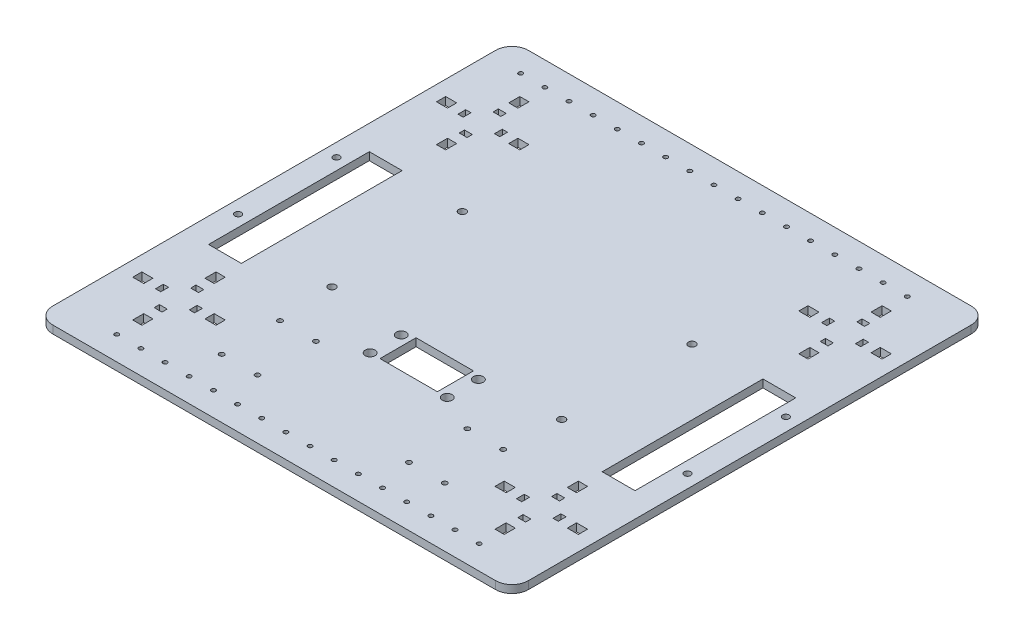
SolidWorks part; units mm, degrees
ref_plane "Front Plane" through (0, 0, 0) normal (0, 0, 1) x (1, 0, 0)
ref_plane "Top Plane" through (0, 0, 0) normal (0, 1, 0) x (1, 0, 0)
ref_plane "Right Plane" through (0, 0, 0) normal (1, 0, 0) x (0, 0, -1)
sketch "Sketch1" plane through (0, 0, 0) normal (0, 1, 0) x (1, 0, 0)
  line L0 (-145, 130.5) -> (145, 130.5) construction
  line L1 (145, -145) -> (-145, -145)
  line L2 (145, -145) -> (145, 145)
  line L3 (145, 145) -> (-145, 145)
  line L4 (-145, -145) -> (-145, 145)
  line L5 (145, -145) -> (-145, 145) construction
  line L6 (145, 145) -> (-145, -145) construction
  line L7 (-145, 116) -> (145, 116) construction
  line L8 (-145, 101.5) -> (145, 101.5) construction
  line L9 (-145, 87) -> (145, 87) construction
  line L10 (-145, 72.5) -> (145, 72.5) construction
  line L11 (-145, 58) -> (145, 58) construction
  line L12 (-145, 43.5) -> (145, 43.5) construction
  line L13 (-145, 29) -> (145, 29) construction
  line L14 (-145, 14.5) -> (145, 14.5) construction
  line L15 (-145, 0) -> (145, 0) construction
  line L16 (-145, -14.5) -> (145, -14.5) construction
  line L17 (-145, -29) -> (145, -29) construction
  line L18 (-145, -43.5) -> (145, -43.5) construction
  line L19 (-145, -58) -> (145, -58) construction
  line L20 (-145, -72.5) -> (145, -72.5) construction
  line L21 (-145, -87) -> (145, -87) construction
  line L22 (-145, -101.5) -> (145, -101.5) construction
  line L23 (-145, -116) -> (145, -116) construction
  line L24 (-145, -130.5) -> (145, -130.5) construction
  line L25 (-145, -145) -> (145, -145) construction
  point P0 (0, 0)
  dimension "D1" = 290
  dimension "D2" = 290
  dimension "D3" = 14.5
  dimension "D5" = 14.5
  dimension "D4" = 20
extrude "Base Plate" add sketch "Sketch1" along normal blind 4.7625
hole_wizard "Caster Holes" positions "Sketch2" profile "Sketch3" hole size "M2" standard "ANSI Metric" end condition through all
sketch "Sketch2" plane through (0, 4.7625, 0) normal (0, 1, 0) x (1, 0, 0)
  line L5 (0, -145) -> (0, 145) construction
  line L6 (145, 145) -> (-145, 145) construction
  line L8 (-145, 0) -> (145, 0) construction
  line L9 (-145, 0) -> (145, 0) construction
  line L10 (-145, 130.5) -> (145, 130.5) construction
  point P200 (-7.366, 130.5)
  point P217 (-22.098, 130.5)
  point P218 (-36.83, 130.5)
  point P219 (-51.562, 130.5)
  point P220 (-66.294, 130.5)
  point P221 (-81.026, 130.5)
  point P222 (-95.758, 130.5)
  point P223 (-110.49, 130.5)
  point P224 (110.49, 130.5)
  point P225 (95.758, 130.5)
  point P226 (81.026, 130.5)
  point P227 (66.294, 130.5)
  point P228 (51.562, 130.5)
  point P229 (36.83, 130.5)
  point P230 (22.098, 130.5)
  point P231 (7.366, 130.5)
  point P232 (7.366, -130.5)
  point P233 (22.098, -130.5)
  point P234 (36.83, -130.5)
  point P235 (51.562, -130.5)
  point P236 (66.294, -130.5)
  point P237 (81.026, -130.5)
  point P238 (95.758, -130.5)
  point P239 (110.49, -130.5)
  point P240 (-110.49, -130.5)
  point P241 (-95.758, -130.5)
  point P242 (-81.026, -130.5)
  point P243 (-66.294, -130.5)
  point P244 (-51.562, -130.5)
  point P245 (-36.83, -130.5)
  point P246 (-22.098, -130.5)
  point P247 (-7.366, -130.5)
  point P250 (-125.222, 130.5)
  dimension "D1" = 7.366
  dimension "D3" = 14.732
  dimension "D2" = 9
sketch "Sketch3" plane through (-125.222, 4.7625, -130.5) normal (1, 0, 0) x (0, 0, 1)
  line L0 (0, 0) -> (0, 4.7625)
  line L1 (0, 4.7625) -> (1.3, 4.7625)
  line L2 (1.3, 4.7625) -> (1.3, 0)
  line L5 (1.3, 0) -> (0, 0)
  line L11 (0, -6.35) -> (0, 107.95) construction
  dimension "Thru Hole Dia." = 2.6
  dimension "Thru Hole Depth" = 4.7625
fillet "Fillet1" radius 10 4 edges at (145, 2.3813, 145) (-145, 2.3813, 145) (145, 2.3813, -145) (-145, 2.3813, -145)
sketch "Sketch4" plane through (0, 0, 0) normal (0, -1, 0) x (1, 0, 0)
  line L0 (145, 0) -> (-145, 0) construction
  line L1 (-145, -135) -> (-145, 135) construction
  line L2 (0, -145) -> (0, 145) construction
  line L3 (-135, 145) -> (135, 145) construction
  point P6 (0, 0)
  point P12 (0, 0)
sketch "Sketch5" plane through (0, 4.7625, 0) normal (0, 1, 0) x (1, 0, 0)
  line L0 (0, 145) -> (0, -145) construction
  line L1 (145, 0) -> (-145, 0) construction
  line L2 (0, 145) -> (0, -145) construction
  line L3 (-17.5, -63) -> (-17.5, -41)
  line L4 (-17.5, -13) -> (17.5, -13) construction
  line L5 (-17.5, -13) -> (-17.5, 9) construction
  line L6 (-17.5, 9) -> (17.5, 9) construction
  line L7 (17.5, -13) -> (17.5, 9) construction
  line L8 (-17.5, -13) -> (17.5, 9) construction
  line L9 (-17.5, 9) -> (17.5, -13) construction
  line L10 (-17.5, -63) -> (17.5, -63)
  line L11 (17.5, -63) -> (17.5, -41)
  line L12 (-17.5, -41) -> (17.5, -41)
  circle A0 centre (-23.5, 6) radius 3 construction
  circle A2 centre (-23.5, -13) radius 3 construction
  circle A3 centre (23.5, 6) radius 3 construction
  circle A4 centre (23.5, -13) radius 3 construction
  circle A5 centre (-23.5, -44) radius 3
  circle A6 centre (-23.5, -63) radius 3
  circle A7 centre (23.5, -63) radius 3
  circle A8 centre (23.5, -44) radius 3
  point P2 (0, -41)
  point P13 (0, -2)
  dimension "D1" = 6
  dimension "D2" = 23.5
  dimension "D3" = 6
  dimension "D4" = 19
  dimension "D5" = 6
  dimension "D6" = 6
  dimension "D8" = 28
  dimension "D7" = 2
extrude "Reflect Holes" cut sketch "Sketch5" against normal up to surface (4.7625 mm away) up to face at (-7.366, 0, -129.2)
sketch "Sketch6" plane through (0, 4.7625, 0) normal (0, 1, 0) x (1, 0, 0)
  line L0 (-137, 145) -> (-137, -145) construction
  line L1 (135, 145) -> (-135, 145) construction
  line L2 (-135, -145) -> (135, -145) construction
  line L3 (-145, 135) -> (-145, -135) construction
  line L16 (145, 0) -> (-145, 0) construction
  line L17 (0, -145) -> (0, 145) construction
  circle A2 centre (-137, 30) radius 2
  circle A22 centre (-137, -30) radius 2
  circle A23 centre (-70, 39.748) radius 2.25
  circle A25 centre (-70, -39.748) radius 2.25
  circle A26 centre (70, -39.748) radius 2.25
  circle A27 centre (70, 39.748) radius 2.25
  circle A28 centre (137, -30) radius 2
  circle A29 centre (137, 30) radius 2
  point P44 (0, 0)
  point P46 (0, 0)
  dimension "D3" = 4
  dimension "D6" = 70
  dimension "D4" = 4.5
  dimension "D1" = 8
  dimension "D2" = 30
  dimension "D5" = 39.748
extrude "bearing slots" cut sketch "Sketch6" against normal up to surface (4.7625 mm away) up to face at (23.5, 0, 47)
sketch "Sketch7" plane through (0, 4.7625, 0) normal (0, 1, 0) x (1, 0, 0)
  line L0 (-145, 135) -> (-145, -135) construction
  line L9 (-130, 43) -> (-110, 43)
  line L10 (-130, 43) -> (-130, -55)
  line L11 (-130, -55) -> (-110, -55)
  line L12 (-110, 43) -> (-110, -55)
  point P9 (-110, -6)
  dimension "D2" = 98
  dimension "D1" = 20
  dimension "D3" = 15
  dimension "D4" = 6
extrude "wheel slots" cut sketch "Sketch7" against normal up to surface (4.7625 mm away) up to face at (-137, 0, 32)
sketch "Sketch9" plane through (0, 4.7625, 0) normal (0, 1, 0) x (1, 0, 0)
  line L0 (-109, -145) -> (-109, 145) construction
  line L1 (135, 145) -> (-135, 145) construction
  line L2 (-145, 135) -> (-145, -135) construction
  line L3 (-135, -145) -> (135, -145) construction
  line L4 (90, -145) -> (90, 145) construction
  line L5 (145, -135) -> (145, 135) construction
  point P0 (-109, -75)
  point P1 (-109, -115)
  point P2 (90, -95)
  point P8 (-109, 0)
  point P21 (90, 0)
  dimension "D1" = 36
  dimension "D2" = 70
  dimension "D3" = 30
  dimension "D4" = 55
  dimension "D5" = 50
sketch "Sketch13" plane through (0, 4.7625, 0) normal (0, 1, 0) x (1, 0, 0)
  line L0 (0, -145) -> (0, 145) construction
  line L7 (135, 145) -> (-135, 145) construction
  line L17 (145, 0) -> (-145, 0) construction
  line L18 (-145, 135) -> (-145, -135) construction
  point P12 (0, 0)
  point P32 (0, 0)
  point P44 (0.04, 0)
mirror "Mirror1" about plane through (0, 0, 0) normal (1, 0, 0) of "wheel slots"
sketch "Sketch15" plane through (0, 4.7625, 0) normal (0, 1, 0) x (1, 0, 0)
  line L21 (-113.25, 118) -> (-107.662, 118)
  line L22 (-113.25, 118) -> (-113.25, 111.269)
  line L23 (-113.25, 111.269) -> (-107.662, 111.269)
  line L24 (-107.662, 118) -> (-107.662, 111.269)
  line L25 (135, 145) -> (-135, 145) construction
  line L26 (-85.056, 95.394) -> (-91.787, 95.394)
  line L27 (-85.056, 95.394) -> (-85.056, 89.806)
  line L28 (-85.056, 89.806) -> (-91.787, 89.806)
  line L29 (-91.787, 95.394) -> (-91.787, 89.806)
  line L30 (-107.662, 67.2) -> (-107.662, 73.931)
  line L31 (-107.662, 67.2) -> (-113.25, 67.2)
  line L32 (-113.25, 67.2) -> (-113.25, 73.931)
  line L33 (-107.662, 73.931) -> (-113.25, 73.931)
  line L34 (-135.856, 89.806) -> (-129.125, 89.806)
  line L35 (-135.856, 89.806) -> (-135.856, 95.394)
  line L36 (-135.856, 95.394) -> (-129.125, 95.394)
  line L37 (-129.125, 89.806) -> (-129.125, 95.394)
  line L38 (-145, 135) -> (-145, -135) construction
  line L39 (-108.4875, 104.925) -> (-113.25, 104.925)
  line L40 (-122.781, 94.5685) -> (-119.581, 94.5685)
  line L41 (-122.781, 94.5685) -> (-122.781, 89.806)
  line L42 (-122.781, 89.806) -> (-119.581, 89.806)
  line L43 (-119.581, 94.5685) -> (-119.581, 89.806)
  line L44 (-108.4875, 104.925) -> (-108.4875, 101.725)
  line L45 (-108.4875, 101.725) -> (-113.25, 101.725)
  line L46 (-113.25, 104.925) -> (-113.25, 101.725)
  line L47 (-98.131, 90.6315) -> (-98.131, 95.394)
  line L48 (-98.131, 90.6315) -> (-101.331, 90.6315)
  line L49 (-101.331, 90.6315) -> (-101.331, 95.394)
  line L50 (-98.131, 95.394) -> (-101.331, 95.394)
  line L51 (-112.4245, 80.275) -> (-107.662, 80.275)
  line L52 (-112.4245, 80.275) -> (-112.4245, 83.475)
  line L53 (-112.4245, 83.475) -> (-107.662, 83.475)
  line L54 (-107.662, 80.275) -> (-107.662, 83.475)
  point P6 (-110.456, 92.6)
  point P10 (-110.456, 111.269)
  point P25 (-110.456, 92.6)
  point P42 (-110.456, 92.6)
  dimension "D1" = 5.588
  dimension "D2" = 6.731
  dimension "D3" = 27
  dimension "D4" = 25.4
  dimension "D6" = 31.75
  dimension "D7" = 3.2
  dimension "D8" = 4.7625
  dimension "D9" = 13.075
  dimension "D5" = 4
  dimension "D10" = 4
extrude "Cut-Extrude2" cut sketch "Sketch15" against normal up to surface (4.7625 mm away) up to face at (-120, 0, 6)
mirror "Mirror2" about plane through (0, 0, 0) normal (1, 0, 0) of "Cut-Extrude2"
mirror "Mirror3" about plane through (0, 0, 0) normal (0, 0, 1) of "Mirror2"
sketch "Sketch16" plane through (0, 4.7625, 0) normal (0, 1, 0) x (1, 0, 0)
  line L0 (-135, -145) -> (135, -145) construction
  line L1 (-68, -73.437) -> (-46.16, -73.437) construction
  line L2 (-68, -73.437) -> (-68, -109) construction
  line L3 (-68, -109) -> (-46.16, -109) construction
  line L4 (-46.16, -73.437) -> (-46.16, -109) construction
  line L5 (-145, 135) -> (-145, -135) construction
  line L6 (0, 145) -> (0, -145) construction
  circle A0 centre (-68, -73.437) radius 1.5
  circle A1 centre (-46.16, -73.437) radius 1.5
  circle A2 centre (-46.16, -109) radius 1.5
  circle A3 centre (-68, -109) radius 1.5
  circle A4 centre (46.16, -73.437) radius 1.5
  circle A5 centre (46.16, -109) radius 1.5
  circle A6 centre (68, -109) radius 1.5
  circle A7 centre (68, -73.437) radius 1.5
  point P16 (0, 0)
  dimension "D1" = 3
  dimension "D2" = 21.84
  dimension "D3" = 35.563
  dimension "D4" = 36
  dimension "D5" = 77
extrude "Cut-Extrude3" cut sketch "Sketch16" against normal up to surface (4.7625 mm away) up to face at (-110.0432, 0, 81.875)
